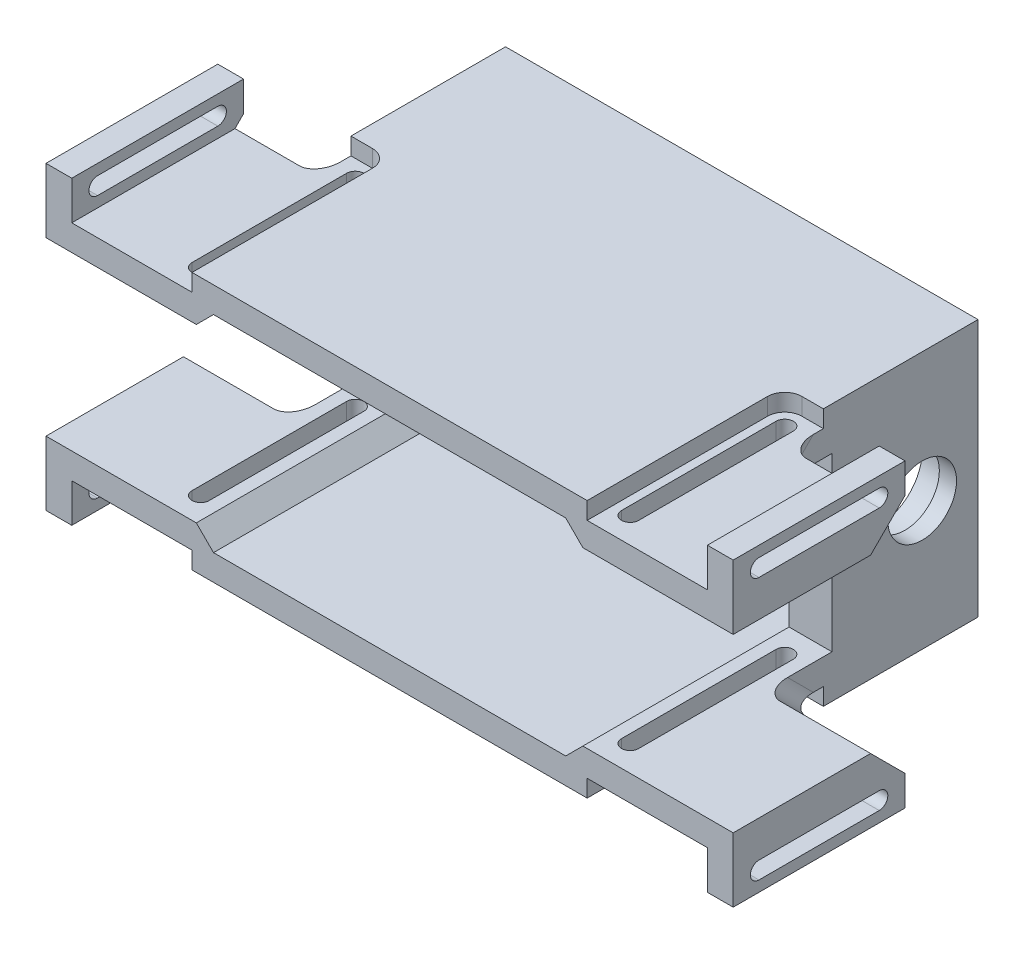
SolidWorks part; units mm, degrees
material "PVC hart"
ref_plane "Ebene vorne" through (0, 0, 0) normal (0, 0, 1) x (1, 0, 0)
ref_plane "Ebene oben" through (0, 0, 0) normal (0, 1, 0) x (1, 0, 0)
ref_plane "Ebene rechts" through (0, 0, 0) normal (1, 0, 0) x (0, 0, -1)
sketch "Skizze1"
  line L0 (-82, 17.5) -> (-82, -17.5) construction
  line L1 (-71, 0) -> (0, 0) construction
  line L8 (-41, 17.5) -> (-41, -17.5) construction
  circle A4 centre (0, 0) radius 29.75 construction
  circle A5 centre (-71, 0) radius 5.75 construction
  circle A6 centre (-47.5, 0) radius 17.75 construction
  circle A7 centre (-47.5, 0) radius 5 construction
  point P8 (0, 0)
  dimension "D2" = 59.5
  dimension "D3" = 11.5
  dimension "D5" = 35.5
  dimension "D6" = 10
  dimension "D7" = 6.5
  dimension "D1" = 11
  dimension "D4" = 71
sketch "Skizze1<4>" plane through (0, 0, 0) normal (1, 0, 0) x (0, 0, -1) same geometry as "Skizze1"
ref_plane "Ebene1" through (0, 0, 82) normal (0, 0, 1) x (1, 0, 0)
ref_plane "Ebene2" through (0, 0, 41) normal (0, 0, 1) x (1, 0, 0)
sketch "Skizze2" plane through (0, 0, 82) normal (0, 0, 1) x (1, 0, 0)
  line L0 (0, 15) -> (0, -15) construction
  line L1 (-27.5, 15) -> (27.5, 15)
  line L2 (-27.5, 15) -> (-27.5, -15)
  line L3 (-27.5, -15) -> (27.5, -15)
  line L4 (27.5, 15) -> (27.5, -15)
  line L5 (-22.5, 0) -> (22.5, 0) construction
  line L6 (-22.5, 12) -> (22.5, 12)
  line L7 (-22.5, 12) -> (-22.5, -12)
  line L8 (-22.5, -12) -> (22.5, -12)
  line L9 (22.5, 12) -> (22.5, -12)
  dimension "D1" = 30
  dimension "D2" = 55
  dimension "D3" = 3
  dimension "D4" = 5
extrude "Aufsatz-Linear austragen1" add sketch "Skizze2" against normal up to surface (41 mm away) up to plane "Ebene2"
sketch "Skizze5" plane through (0, 0, 82) normal (0, 0, 1) x (1, 0, 0)
  line L0 (-27.5, 15) -> (-27.5, -15) construction
  line L1 (-27.5, 10) -> (27.5, 10)
  line L2 (-27.5, 10) -> (-27.5, -10)
  line L3 (-27.5, -10) -> (27.5, -10)
  line L4 (27.5, 10) -> (27.5, -10)
  line L5 (27.5, -15) -> (27.5, 15) construction
  line L8 (-27.5, 0) -> (27.5, 0) construction
  dimension "D1" = 20
extrude "Schnitt-Linear austragen3" cut sketch "Skizze5" against normal blind 24
sketch "Skizze4" plane through (22.5, 0, 0) normal (1, 0, 0) x (0, 0, -1)
  circle A0 centre (-47.5, 0) radius 5
  circle A1 centre (-47.5, 0) radius 4
  dimension "D1" = 10
  dimension "D2" = 8
extrude "Schnitt-Linear austragen1" cut sketch "Skizze4" against normal through all contours A1
extrude "Schnitt-Linear austragen2" cut sketch "Skizze4<3>" along normal blind 3 contours A0
sketch "Skizze4<3>" plane through (22.5, 0, 0) normal (1, 0, 0) x (0, 0, -1) same geometry as "Skizze4"
sketch "Skizze6" plane through (0, 15, 0) normal (0, 1, 0) x (1, 0, 0)
  line L0 (25, -61) -> (25, -79) construction
  line L1 (26, -61) -> (26, -79)
  line L2 (24, -61) -> (24, -79)
  line L3 (25, -61) -> (25, -79) construction
  line L4 (27, -61) -> (27, -79)
  line L5 (23, -61) -> (23, -79)
  line L7 (25, -61) -> (25, -58) construction
  line L8 (22.5, -58) -> (27.5, -58) construction
  line L9 (25, -79) -> (25, -82) construction
  line L10 (27.5, -82) -> (-27.5, -82) construction
  line L11 (25, -59) -> (27.5, -59)
  line L12 (27.5, -41) -> (27.5, -82) construction
  line L13 (27.5, -59) -> (27.5, -82)
  line L14 (27.5, -82) -> (23, -82)
  line L15 (23, -82) -> (23, -79)
  arc A0 (26, -61) -> (24, -61) centre (25, -61) ccw
  arc A1 (24, -79) -> (26, -79) centre (25, -79) ccw
  arc A2 (27, -61) -> (23, -61) centre (25, -61) ccw
  arc A3 (23, -79) -> (27, -79) centre (25, -79) ccw
  point P2 (25, -70)
  point P8 (25, -70)
  line M3 (-27.5, -82) -> (27.5, -82)
  line M4 (27.5, -82) -> (27.5, -41)
  dimension "D1" = 2
  dimension "D2" = 4
  dimension "D3" = 3
extrude "Schnitt-Linear austragen4" cut sketch "Skizze6" against normal up to next contours L2 A1 L1 A0
extrude "Schnitt-Linear austragen5" cut sketch "Skizze6<3>" against normal blind 2 contours L5 A3 L4 A2 A1 L2 A0 L1 | A3 L15 L11 A2 L4 M3 M4 region at (26.5799, 15, 59.4201) region at (26.7764, 15, 70)
sketch "Skizze6<3>" plane through (0, 15, 0) normal (0, 1, 0) x (1, 0, 0) same geometry as "Skizze6"
sketch "Skizze8" plane through (0, 0, 82) normal (0, 0, 1) x (1, 0, 0)
  line L0 (27.5, 13) -> (37, 13)
  line L1 (37, 13) -> (37, 17.5)
  line L2 (37, 17.5) -> (40, 17.5)
  line L3 (40, 17.5) -> (40, 10)
  line L4 (40, 10) -> (27.5, 10)
  line L6 (27.5, 10) -> (27.5, 13)
  line L9 (0, 15) -> (0, -15) construction
  line L11 (-27.5, -15) -> (27.5, -15) construction
  line L12 (-27.5, 0) -> (27.5, 0) construction
  line L13 (-27.5, 10) -> (-27.5, -10) construction
  line L14 (27.5, -10) -> (27.5, 10) construction
  line L15 (23, 15) -> (-27.5, 15) construction
  line L16 (0, 200017.5) -> (0, -200017.5) construction
  dimension "D1" = 80
  dimension "D2" = 3
  dimension "D3" = 35
  dimension "D4" = 3
  dimension "D5" = 4.5
extrude "Aufsatz-Linear austragen2" add sketch "Skizze8" against normal offset from surface (20 mm away) 4 up to face at (25, 0, 58)
sketch "Skizze9" plane through (37, 0, 0) normal (-1, 0, 0) x (0, 0, 1)
  line L0 (65, 15.25) -> (79, 15.25) construction
  line L1 (65, 16.25) -> (79, 16.25)
  line L2 (65, 14.25) -> (79, 14.25)
  line L6 (79, 15.25) -> (82, 15.25) construction
  line L7 (82, 17.5) -> (82, 13) construction
  line L8 (65, 15.25) -> (62, 15.25) construction
  line L9 (62, 13) -> (62, 17.5) construction
  arc A0 (65, 16.25) -> (65, 14.25) centre (65, 15.25) ccw
  arc A1 (79, 14.25) -> (79, 16.25) centre (79, 15.25) ccw
  point P2 (72, 15.25)
  dimension "D1" = 2
  dimension "D2" = 3
extrude "Schnitt-Linear austragen6" cut sketch "Skizze9" against normal through all
mirror "Spiegeln2" about plane through (0, 0, 0) normal (0, 1, 0) of "Schnitt-Linear austragen6", "Schnitt-Linear austragen5", "Schnitt-Linear austragen4", "Aufsatz-Linear austragen2"
mirror "Spiegeln1" about plane through (0, 0, 0) normal (1, 0, 0) of "Schnitt-Linear austragen2", "Spiegeln2", "Schnitt-Linear austragen1"
chamfer "Fase2" distance 2 angle 45 4 edges at (-22.5, 12, 61.5) (-22.5, -12, 61.5) (22.5, -12, 61.5) (22.5, 12, 61.5)
chamfer "Fase3" distance 4 angle 45 4 edges at (-33.75, 10, 62) (33.75, -10, 62)
fillet "Verrundung1" radius 2 4 edges at (-27.5, 11.5, 64.5) (-27.5, -11.5, 64.5) (27.5, -11.5, 64.5) (27.5, 11.5, 64.5)
